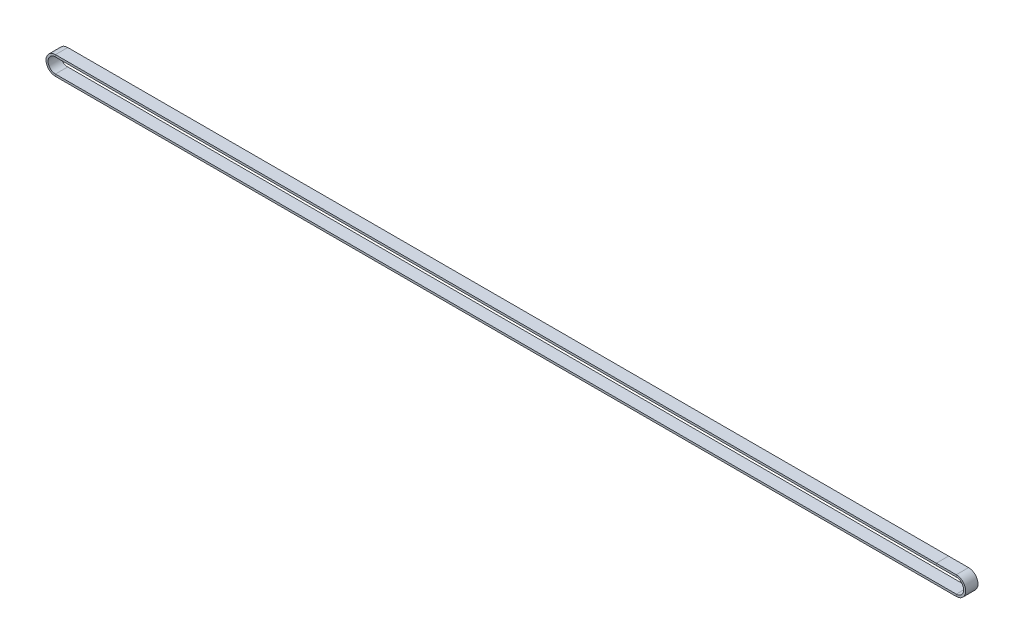
SolidWorks part; units mm, degrees
ref_plane "Front Plane" through (0, 0, 0) normal (0, 0, 1) x (1, 0, 0)
ref_plane "Top Plane" through (0, 0, 0) normal (0, 1, 0) x (1, 0, 0)
ref_plane "Right Plane" through (0, 0, 0) normal (1, 0, 0) x (0, 0, -1)
ref_plane "Plane1" through (-16, 0, 0) normal (1, 0, 0) x (0, 0, -1)
sketch "Sketch2" plane through (0, 0, 0) normal (0, 0, 1) x (1, 0, 0)
  line L0 (0, 0) -> (1, 0) construction
  line L1 (0, 0) -> (0, 1) construction
  line L2 (-1.4, -6.9) -> (-660.3327, -6.9)
  line L3 (-660.3327, 6.9) -> (-1.4, 6.9)
  arc A0 (-1.4, 6.9) -> (-1.4, -6.9) centre (-1.4, 0) cw
  arc A1 (-660.3327, -6.9) -> (-660.3327, 6.9) centre (-660.3327, 0) cw
sketch "Sketch3" plane through (-16, 0, 0) normal (1, 0, 0) x (0, 0, -1)
  line L1 (0, 6.9) -> (-9, 6.9)
  line L2 (0, 6.9) -> (0, 5.4)
  line L3 (0, 5.4) -> (-9, 5.4)
  line L4 (-9, 6.9) -> (-9, 5.4)
  dimension "D1" = 1.5
  dimension "D2" = 9
sweep "Sweep1" add profiles "Sketch3" path "Sketch2"
move or copy body "Body-Move/Copy1" [suppressed] bodies to move or copy 101
